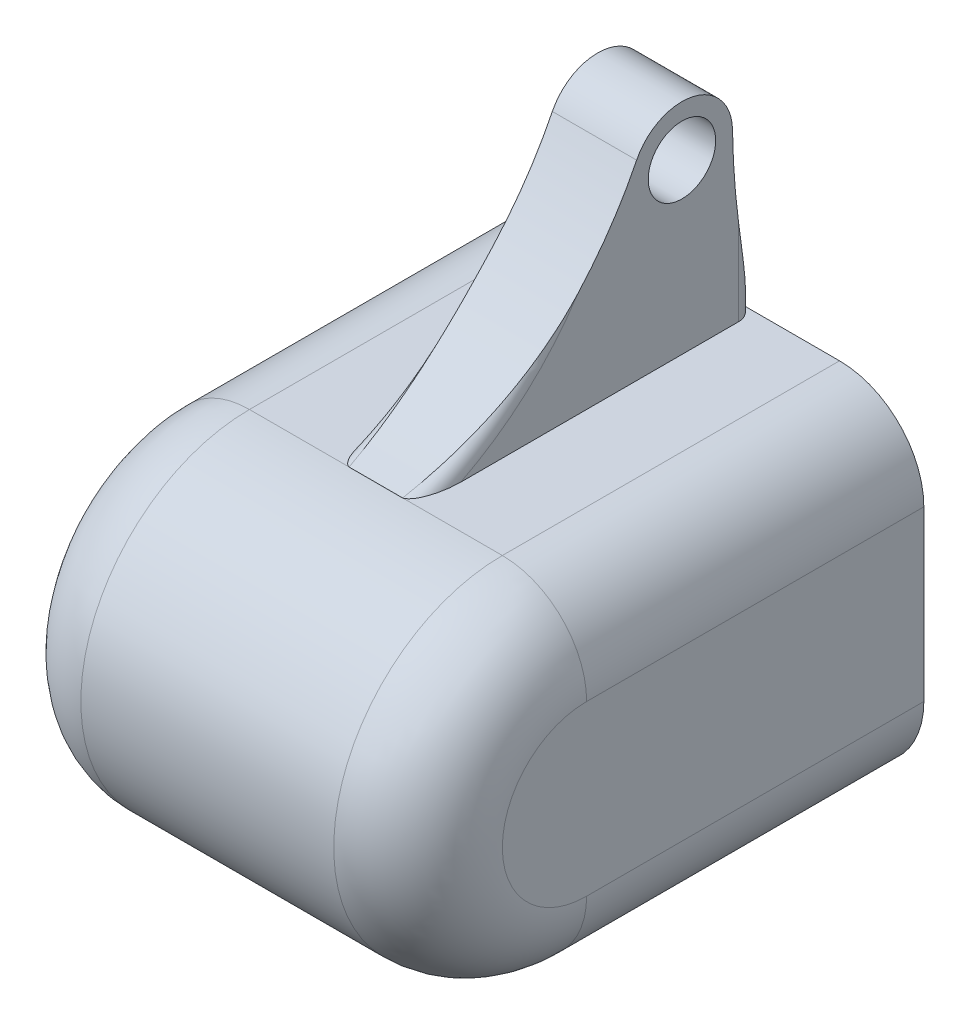
SolidWorks part; units mm, degrees
material "Nailon 6/10"
ref_plane "Alzado" through (0, 0, 0) normal (0, 0, 1) x (1, 0, 0)
ref_plane "Planta" through (0, 0, 0) normal (0, 1, 0) x (1, 0, 0)
ref_plane "Vista lateral" through (0, 0, 0) normal (1, 0, 0) x (0, 0, -1)
sketch "Croquis1" plane through (0, 0, 0) normal (1, 0, 0) x (0, 0, -1)
  line L0 (0, 0) -> (20, 0)
  line L1 (0, 20) -> (20, 20)
  line L2 (20, 20) -> (20, 0)
  arc A0 (0, 0) -> (0, 20) centre (0, 10) cw
  dimension "D2" = 10
  dimension "D1" = 20
  dimension "D3" = 20
extrude "Saliente-Extruir1" add sketch "Croquis1" along normal blind 25
fillet "Redondeo1" radius 5 6 edges at (0, 0, -10) (0, 10, 10) (25, 0, -10) (25, 10, 10) (0, 20, -10) (25, 20, -10)
shell "Vaciado1" thickness 2 removed face at (12.5, 10, -20)
ref_plane "Plano1" through (12.5, 0, 0) normal (1, 0, 0) x (0, 0, -1)
sketch "Croquis3" plane through (12.5, 0, 0) normal (1, 0, 0) x (0, 0, -1)
  line L0 (0, 20) -> (20, 20) construction
  line L1 (20, 20) -> (20, 33.9901)
  line L2 (20, 33.9901) -> (11.3049, 33.9901)
  line L3 (-0.0121, 20) -> (20, 20)
  arc A0 (-0.0121, 20) -> (11.3049, 33.9901) centre (-5.644, 36.1282) ccw
extrude "Saliente-Extruir2" add sketch "Croquis3" along normal mid plane 5
fillet "Redondeo3" radius 1 6 edges at (15, 33.9901, -15.6525) (15, 26.9951, -20) (15, 25.3842, -7.6378) (10, 26.9951, -20) (10, 25.3842, -7.6378) (10, 33.9901, -15.6525)
sketch "Croquis4" plane through (15, 0, 0) normal (1, 0, 0) x (0, 0, -1)
  line L0 (15.6525, 33.9901) -> (15.6525, 20) construction
  line L1 (11.3049, 33.9901) -> (20, 33.9901) construction
  line L2 (19, 20) -> (2.5343, 20) construction
  circle A0 centre (15.6525, 29.9901) radius 2
  dimension "D1" = 4
  dimension "D2" = 4
extrude "Cortar-Extruir1" cut sketch "Croquis4" against normal through all
sketch "Croquis5" plane through (15, 0, 0) normal (1, 0, 0) x (0, 0, -1)
  line L0 (0, 20) -> (20, 20)
  line L2 (-7.217, 39.7816) -> (25.5715, 39.7816)
  line L3 (-7.217, 39.7816) -> (-7.217, 20)
  line L4 (-7.217, 20) -> (25.5715, 20)
  line L5 (25.5715, 39.7816) -> (25.5715, 20)
  circle A0 centre (15.6525, 29.9901) radius 3
  circle A1 centre (15.6525, 29.9901) radius 2 construction
  arc A2 (0, 20) -> (12.9656, 31.3245) centre (-7.217, 41.3474) ccw
  arc A4 (-0.0121, 20) -> (11.3049, 33.9901) centre (-5.644, 36.1282) ccw construction
  arc A5 (20, 20) -> (18.6522, 30.0334) centre (61.2443, 30.6478) cw
  line M2 (19, 32.9901) -> (12.1649, 32.9901)
  arc M3 (12.1649, 32.9901) -> (2.5343, 20) centre (-5.644, 36.1282) cw
  line M5 (19, 20) -> (19, 32.9901)
  dimension "D1" = 1
extrude "Cortar-Extruir2" cut sketch "Croquis5" against normal blind 10 contours A5 L4 L5 L2 L3 A2 M3 M2 M5 | A2 A0 M3 M2 | A5 A0 M5 M2 region at (15, 31.1423, -8.0495) region at (15, 30.9065, -12.2445) region at (15, 27.6083, -18.8415)
